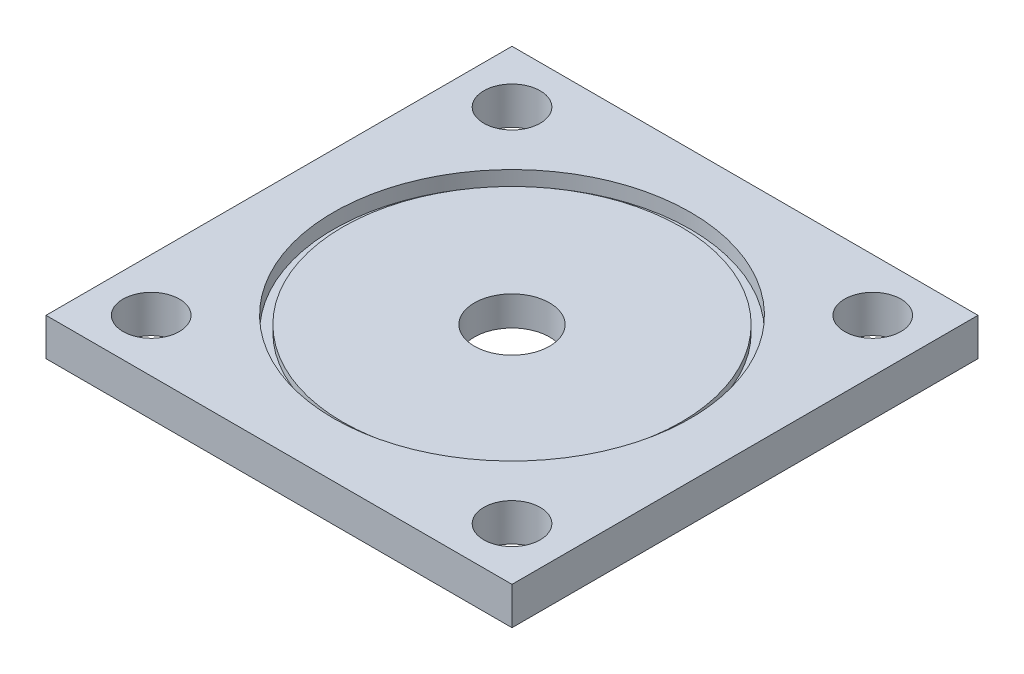
SolidWorks part; units mm, degrees
ref_plane "Front Plane" through (0, 0, 0) normal (0, 0, 1) x (1, 0, 0)
ref_plane "Top Plane" through (0, 0, 0) normal (0, 1, 0) x (1, 0, 0)
ref_plane "Right Plane" through (0, 0, 0) normal (1, 0, 0) x (0, 0, -1)
sketch "plateOutline" plane through (0, 0, 0) normal (0, 1, 0) x (1, 0, 0)
  line L1 (-39.37, -39.37) -> (39.37, -39.37)
  line L2 (-39.37, -39.37) -> (-39.37, 39.37)
  line L3 (-39.37, 39.37) -> (39.37, 39.37)
  line L4 (39.37, -39.37) -> (39.37, 39.37)
  line L5 (-39.37, -39.37) -> (39.37, 39.37) construction
  line L6 (-39.37, 39.37) -> (39.37, -39.37) construction
  line L7 (-39.37, -39.37) -> (39.37, -39.37) construction
  line L8 (-39.37, -39.37) -> (-39.37, 39.37) construction
  line L9 (-39.37, 39.37) -> (39.37, 39.37) construction
  line L10 (39.37, -39.37) -> (39.37, 39.37) construction
  point P0 (0, 0)
  dimension "D1" = 78.74
sketch "railGuides" plane through (0, 0, 0) normal (0, 1, 0) x (1, 0, 0)
  line L0 (-30.48, 30.48) -> (30.48, 30.48) construction
  line L1 (30.48, -30.48) -> (30.48, 30.48) construction
  line L2 (-30.48, -30.48) -> (30.48, -30.48) construction
  line L3 (-30.48, -30.48) -> (-30.48, 30.48) construction
  line L5 (-40.005, -40.005) -> (40.005, -40.005) construction
  line L11 (-40.005, -40.005) -> (-40.005, 40.005) construction
  line L12 (-40.005, 40.005) -> (40.005, 40.005) construction
  line L13 (40.005, -40.005) -> (40.005, 40.005) construction
  line L14 (-40.005, -40.005) -> (40.005, 40.005) construction
  line L15 (-40.005, 40.005) -> (40.005, -40.005) construction
  circle A0 centre (-30.48, 30.48) radius 4.7625
  circle A1 centre (30.48, 30.48) radius 4.7625
  circle A2 centre (30.48, -30.48) radius 4.7625
  circle A3 centre (-30.48, -30.48) radius 4.7625
  point P1 (0, 0)
  dimension "D1" = 80.01
  dimension "D3" = 9.525
  dimension "D4" = 9.525
  dimension "D5" = 9.525
  dimension "D6" = 9.525
  dimension "D7" = 9.525
  dimension "D2" = 80.01
sketch "FuelGrainMounting" plane through (0, 0, 0) normal (0, 1, 0) x (1, 0, 0)
  circle A0 centre (0, 0) radius 30.1625
  dimension "D1" = 60.325
sketch "GasIntake" plane through (0, 0, 0) normal (0, 1, 0) x (1, 0, 0)
  line L0 (-39.37, 39.37) -> (39.37, -39.37) construction
  circle A0 centre (0, 0) radius 6.35
  dimension "D1" = 12.7
extrude "Boss-Extrude1" add sketch "plateOutline" along normal blind 6.35 contours L3 L4 L1 L2
extrude "Cut-Extrude1" cut sketch "railGuides" along normal blind 10 contours A0 | A3 | A1 | A2 region at (-30.48, 0, -30.48)
extrude "Cut-Extrude2" cut sketch "FuelGrainMounting" along normal blind 5 from offset 5
extrude "Cut-Extrude3" cut sketch "GasIntake" along normal blind 5
sketch "Sketch1" plane through (0, 0, 0) normal (0, 1, 0) x (1, 0, 0)
  circle A0 centre (0, 0) radius 28.575
  circle A2 centre (0, 0) radius 30.1625
  dimension "D1" = 60.325
  dimension "D2" = 57.15
extrude "Cut-Extrude4" cut sketch "Sketch1" against normal blind 1.143 from offset 5
